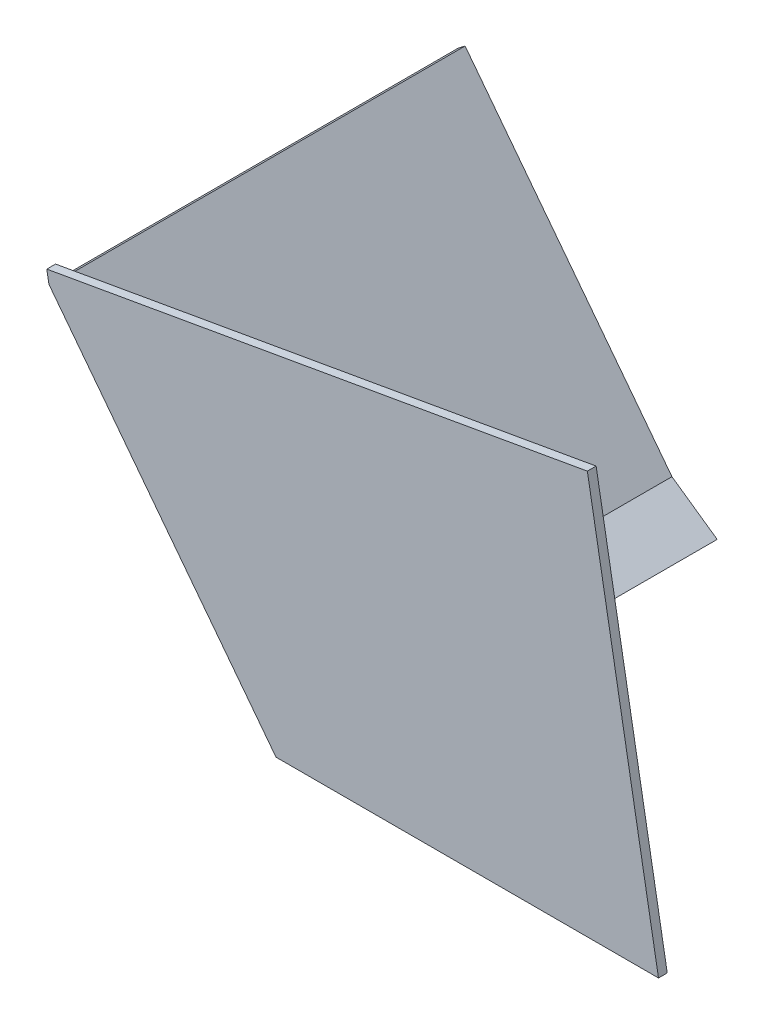
SolidWorks part; units mm, degrees
ref_plane "Front Plane" through (0, 0, 0) normal (0, 0, 1) x (1, 0, 0)
ref_plane "Top Plane" through (0, 0, 0) normal (0, 1, 0) x (1, 0, 0)
ref_plane "Right Plane" through (0, 0, 0) normal (1, 0, 0) x (0, 0, -1)
ref_axis "Axis1" through (0, 0, -14.8175) along (0, 0, 1)
sketch "Sketch1" plane through (0, 0, 0) normal (0, 0, 1) x (1, 0, 0)
  line L0 (-138.5, 0) -> (138.5, 0) construction
  line L1 (-156.1048, 22.9431) -> (-305.9094, 218.1722)
  line L4 (-146.504, 0) -> (-310.9472, 214.3065)
  line L5 (-310.9472, 214.3065) -> (-305.9094, 218.1722)
  line L9 (-123.3387, 0) -> (-156.1048, 22.9431)
  line L10 (-123.3387, 0) -> (-146.504, 0)
  line L11 (-156.1048, 22.9431) -> (-138.5, 0) construction
  point P4 (0, 0)
  dimension "D1" = 52.5
  dimension "D2" = 35
  dimension "D3" = 277
  dimension "D4" = 275
  dimension "D5" = 40
  dimension "D6" = 6.35
extrude "Boss-Extrude1" add sketch "Sketch1" along normal blind 290
sketch "Sketch2" plane through (0, 0, 290) normal (0, 0, 1) x (1, 0, 0)
  line L0 (-146.504, 0) -> (-310.9472, 214.3065)
  line L1 (-312.502, 223.1244) -> (78.9815, 292.1535)
  line L3 (130.496, 0) -> (-146.504, 0)
  line L4 (-310.9472, 214.3065) -> (-146.504, 0) construction
  line L7 (-310.9472, 214.3065) -> (-312.502, 223.1244)
  line L8 (-305.9094, 218.1722) -> (-310.9472, 214.3065) construction
  line L9 (103.1846, 0) -> (-103.1846, 0) construction
  line L10 (130.496, 0) -> (78.9815, 292.1535)
  line L11 (-146.504, 0) -> (-123.3387, 0) construction
  point P8 (0, 0)
  point P9 (0, 0)
  point P13 (-141.3123, -6.766)
  dimension "D1" = 10
  dimension "D2" = 274
  dimension "D3" = 277
extrude "Boss-Extrude2" add sketch "Sketch2" along normal blind 6.35
ref_plane "Plane1" through (0, 0, 0) normal (0.9848, 0.1736, 0) x (0, 0, 1)
